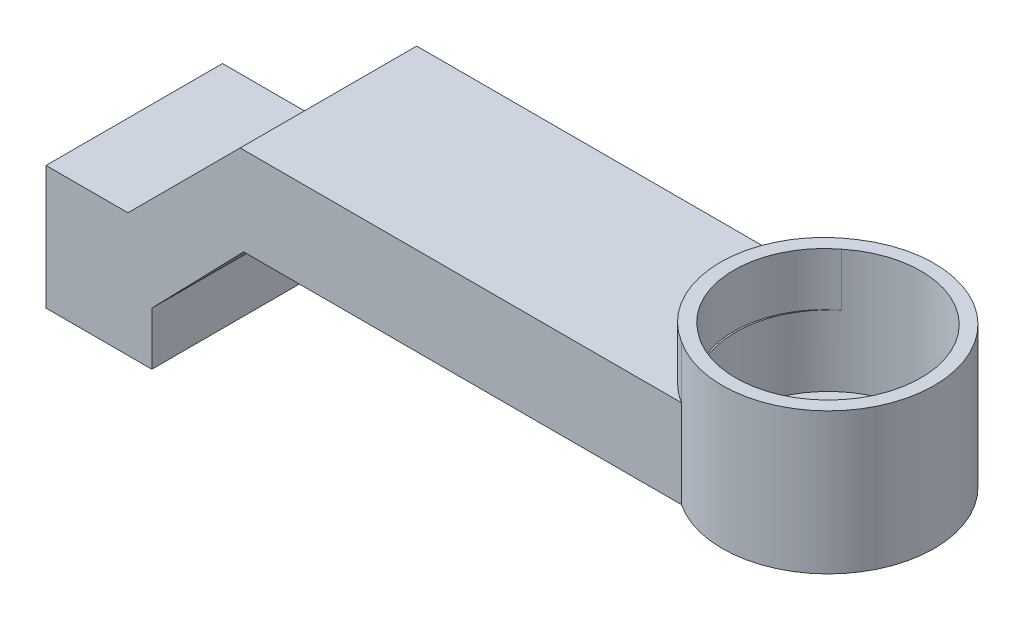
SolidWorks part; units mm, degrees
ref_plane "Front Plane" through (0, 0, 0) normal (0, 0, 1) x (1, 0, 0)
ref_plane "Top Plane" through (0, 0, 0) normal (0, 1, 0) x (1, 0, 0)
ref_plane "Right Plane" through (0, 0, 0) normal (1, 0, 0) x (0, 0, -1)
sketch "Sketch2" plane through (0, 0, 0) normal (0, 0, 1) x (1, 0, 0)
  line L1 (6.476, 10.358) -> (31.476, 10.358)
  line L2 (31.476, 10.358) -> (31.476, 5.358)
  line L3 (31.476, 5.358) -> (11.456, 5.358)
  line L7 (6.476, 0) -> (11.456, 0)
  line L8 (11.456, 0) -> (11.456, 5.358)
  line L10 (6.476, 0) -> (6.476, 10.358)
  dimension "D1" = 25
  dimension "D2" = 5
  dimension "D3" = 10.358
  dimension "D4" = 6.476
  dimension "D6" = 4.98
extrude "Boss-Extrude1" add sketch "Sketch2" along normal blind 10
sketch "Sketch6" plane through (0, 5.358, 0) normal (0, -1, 0) x (1, 0, 0)
  line L0 (31.476, 0) -> (31.476, 10)
  arc A0 (31.476, 10) -> (31.476, 0) centre (34.7926, 5) cw
  dimension "D1" = 6
extrude "Boss-Extrude4" add sketch "Sketch6" against normal blind 8
sketch "Sketch7" plane through (0, 13.358, 0) normal (0, 1, 0) x (1, 0, 0)
  line L0 (34.7926, 1) -> (34.7926, -11) construction
  arc A0 (31.476, -10) -> (31.476, 0) centre (34.7926, -5) ccw construction
  circle A1 centre (34.7926, -5) radius 5.25
  dimension "D1" = 10.5
extrude "Cut-Extrude1" cut sketch "Sketch7" against normal blind 7
sketch "Sketch8" plane through (6.476, 0, 0) normal (-1, 0, 0) x (0, 0, 1)
  line L0 (10, 10.358) -> (10, 0) construction
  line L1 (0, 0) -> (10, 0)
  line L2 (0, 0) -> (0, 4)
  line L3 (0, 4) -> (10, 4)
  line L4 (10, 0) -> (10, 4)
  dimension "D1" = 4
extrude "Boss-Extrude5" add sketch "Sketch8" along normal blind 11
sketch "Sketch9" plane through (0, 0, 10) normal (0, 0, 1) x (1, 0, 0)
  line L0 (11.456, 5.358) -> (6.259, 0)
  line L1 (-4.524, 0) -> (11.456, 0) construction
  line L2 (6.259, 0) -> (11.456, 0)
  line L3 (11.456, 0) -> (11.456, 5.358)
  dimension "D1" = 7.4644
extrude "Cut-Extrude2" cut sketch "Sketch9" against normal blind 10
sketch "Sketch10" plane through (0, 10.358, 0) normal (0, 1, 0) x (1, 0, 0)
  line L0 (31.476, -10) -> (31.476, -9.0697)
  line L1 (31.476, -0.9303) -> (31.476, 0)
  arc A0 (31.476, -9.0697) -> (31.476, -0.9303) centre (34.5583, -5) cw
  arc A1 (31.476, 0) -> (31.476, -10) centre (34.5583, -5) ccw
  dimension "D1" = 5.8737
extrude "Boss-Extrude6" add sketch "Sketch10" along normal up to surface (3 mm away) contours A1 L0 A0 L1 up to face at (35.9468, 13.358, 5)
sketch "Sketch11" plane through (0, 0, 10) normal (0, 0, 1) x (1, 0, 0)
  line L0 (6.476, 4) -> (6.476, 10.358)
  line L1 (6.476, 10.358) -> (0.118, 4)
  line L2 (-4.524, 4) -> (6.476, 4) construction
  line L3 (0.118, 4) -> (6.476, 4)
extrude "Boss-Extrude7" add sketch "Sketch11" against normal up to surface (10 mm away) up to face at (10.5714, 4.929, 0)
sketch "Sketch12" plane through (0, 0, 10) normal (0, 0, 1) x (1, 0, 0)
  line L0 (6.259, 0) -> (1.4745, 0)
  line L1 (-4.524, 0) -> (6.259, 0) construction
  line L2 (11.456, 5.358) -> (6.6715, 5.358)
  line L3 (6.6715, 5.358) -> (1.4745, 0)
  line L4 (6.259, 0) -> (11.456, 5.358)
extrude "Cut-Extrude3" cut sketch "Sketch12" against normal blind 10
sketch "Sketch13" plane through (0, 0, 0) normal (0, -1, 0) x (1, 0, 0)
  line L0 (1.4745, 0) -> (1.4745, 10) construction
  line L1 (-4.524, 10) -> (1.4745, 10)
  line L2 (-4.524, 10) -> (-4.524, 0)
  line L3 (-4.524, 0) -> (1.4745, 0)
  line L4 (1.4745, 10) -> (1.4745, 0)
  dimension "D1" = 10
extrude "Boss-Extrude8" add sketch "Sketch13" along normal blind 3
